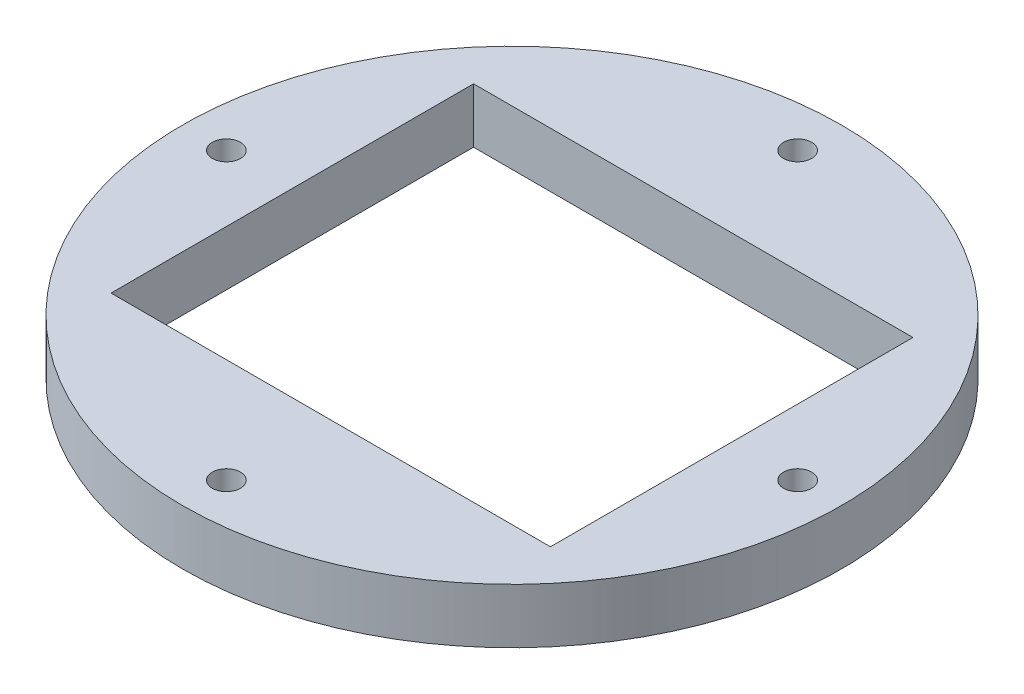
SolidWorks part; units mm, degrees
material "Acrylic (Medium-high impact)"
ref_plane "Front Plane" through (0, 0, 0) normal (0, 0, 1) x (1, 0, 0)
ref_plane "Top Plane" through (0, 0, 0) normal (0, 1, 0) x (1, 0, 0)
ref_plane "Right Plane" through (0, 0, 0) normal (1, 0, 0) x (0, 0, -1)
sketch "Sketch1" plane through (0, 0, 0) normal (0, 1, 0) x (1, 0, 0)
  line L1 (-25.4, -20.955) -> (25.4, -20.955)
  line L2 (-25.4, -20.955) -> (-25.4, 20.955)
  line L3 (-25.4, 20.955) -> (25.4, 20.955)
  line L4 (25.4, -20.955) -> (25.4, 20.955)
  line L5 (-25.4, -20.955) -> (25.4, 20.955) construction
  line L6 (-25.4, 20.955) -> (25.4, -20.955) construction
  circle A0 centre (0, 0) radius 38.1
  circle A1 centre (0, 33.02) radius 1.6256
  circle A2 centre (33.02, 0) radius 1.6256
  circle A3 centre (0, -33.02) radius 1.6256
  circle A4 centre (-33.02, 0) radius 1.6256
  circle A5 centre (0, 33.02) radius 1.6256 construction
  point P14 (0, 0)
  dimension "D1" = 76.2
  dimension "D4" = 33.02
  dimension "D5" = 41.91
  dimension "D6" = 50.8
  dimension "D2" = 4
extrude "Boss-Extrude1" add sketch "Sketch1" along normal blind 6.35
